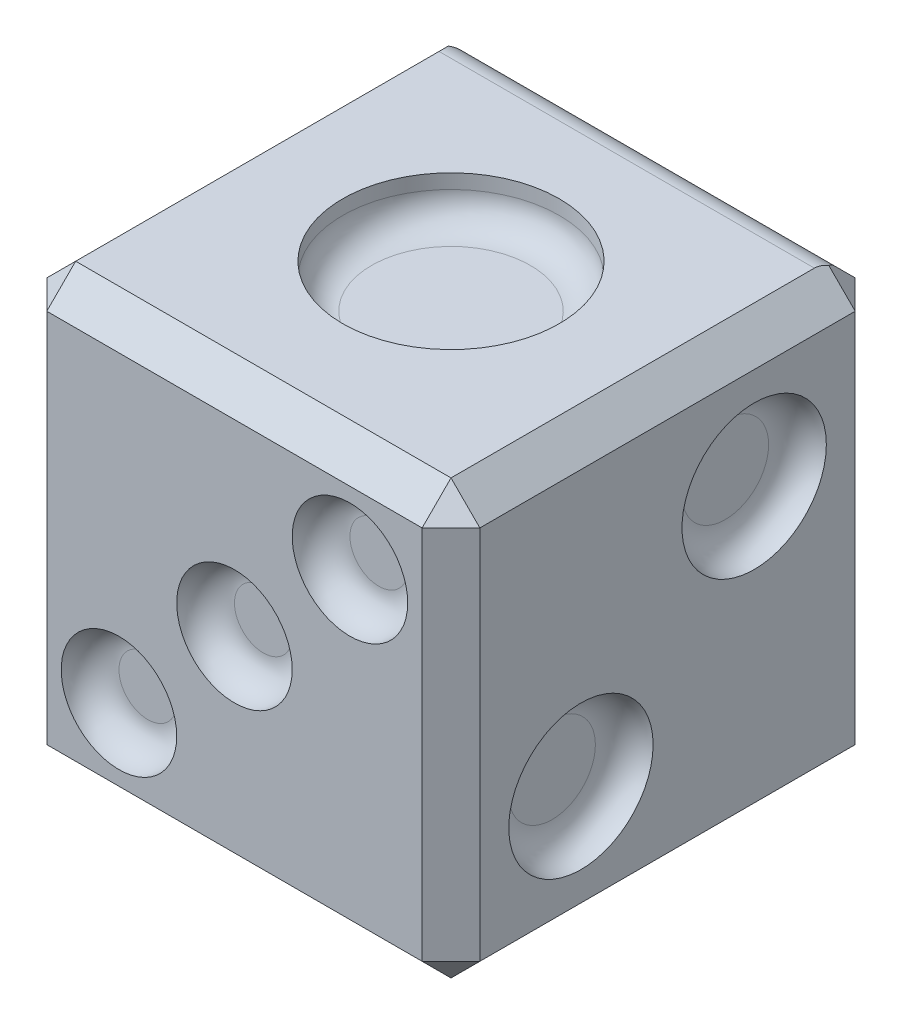
SolidWorks part; units mm, degrees
ref_plane "正面" through (0, 0, 0) normal (0, 0, 1) x (1, 0, 0)
ref_plane "平面" through (0, 0, 0) normal (0, 1, 0) x (1, 0, 0)
ref_plane "右側面" through (0, 0, 0) normal (1, 0, 0) x (0, 0, -1)
sketch "ｽｹｯﾁ7" plane through (0, 0, 0) normal (0, 1, 0) x (1, 0, 0)
  line L1 (0, 0) -> (30, 0)
  line L2 (0, 0) -> (0, 30)
  line L3 (0, 30) -> (30, 30)
  line L4 (30, 0) -> (30, 30)
  dimension "D1" = 30
  dimension "D2" = 30
extrude "ﾎﾞｽ - 押し出し1" add sketch "ｽｹｯﾁ7" along normal blind 30 contours L2 L1 L4 L3
chamfer "面取り2" distance 2 angle 45 12 edges at (0, 15, -30) (0, 15, 0) (30, 15, 0) (0, 30, -15) (15, 30, 0) (30, 30, -15) (15, 30, -30) (30, 15, -30) (0, 0, -15) (15, 0, 0) (30, 0, -15) (15, 0, -30)
sketch "ｽｹｯﾁ11" plane through (0, 30, 0) normal (0, 1, 0) x (1, 0, 0)
  line L0 (2, 28) -> (2, 2) construction
  line L1 (2, 2) -> (28, 2) construction
  circle A0 centre (15, 15) radius 7.5
  dimension "D1" = 15
  dimension "D2" = 13
  dimension "D3" = 13
extrude "ｶｯﾄ - 押し出し4" cut sketch "ｽｹｯﾁ11" against normal blind 3 contours A0
fillet "ﾌｨﾚｯﾄ1" radius 2 1 edges at (15, 27, -7.5)
sketch "ｽｹｯﾁ12" plane through (0, 0, 0) normal (0, 0, 1) x (1, 0, 0)
  line L0 (0, 2) -> (0, 28) construction
  line L1 (28, 0) -> (2, 0) construction
  line L2 (2, 30) -> (28, 30) construction
  line L3 (30, 28) -> (30, 2) construction
  circle A0 centre (23, 23) radius 4
  circle A1 centre (15, 15) radius 4
  circle A2 centre (7, 7) radius 4
  dimension "D3" = 8
  dimension "D6" = 8
  dimension "D9" = 8
  dimension "D1" = 7
  dimension "D2" = 7
  dimension "D4" = 7
  dimension "D5" = 7
  dimension "D7" = 15
  dimension "D8" = 15
extrude "ｶｯﾄ - 押し出し5" cut sketch "ｽｹｯﾁ12" against normal blind 2 contours A0 | A1 | A2
fillet "ﾌｨﾚｯﾄ2" radius 2 3 edges at (27, 23, -2) (19, 15, -2) (11, 7, -2)
sketch3d "3Dｽｹｯﾁ1"
  point P0 (25.9316, 13.2015, 0)
sketch "ｽｹｯﾁ13" plane through (0, 0, 0) normal (0, -1, 0) x (1, 0, 0)
  line L0 (28, -30) -> (2, -30) construction
  line L1 (0, -28) -> (0, -2) construction
  line L2 (30, -2) -> (30, -28) construction
  line L3 (2, 0) -> (28, 0) construction
  circle A0 centre (7.5, -6.5) radius 4
  circle A1 centre (7.5, -15) radius 4
  circle A2 centre (7.5, -23.5) radius 4
  circle A3 centre (22.5, -23.5) radius 4
  circle A4 centre (22.5, -15) radius 4
  circle A5 centre (22.5, -6.5) radius 4
  dimension "D1" = 8
  dimension "D2" = 8
  dimension "D3" = 8
  dimension "D4" = 8
  dimension "D5" = 8
  dimension "D6" = 8
  dimension "D9" = 6.5
  dimension "D16" = 15
  dimension "D7" = 6.5
  dimension "D8" = 7.5
  dimension "D10" = 7.5
  dimension "D11" = 6.5
  dimension "D12" = 7.5
  dimension "D13" = 7.5
  dimension "D14" = 6.5
  dimension "D15" = 7.5
  dimension "D17" = 15
  dimension "D18" = 7.5
extrude "ｶｯﾄ - 押し出し6" cut sketch "ｽｹｯﾁ13" against normal blind 2 contours A0 | A5 | A4 | A3 | A2 | A1
fillet "ﾌｨﾚｯﾄ3" radius 2 7 edges at (22.5, 2, -27.5) (7.5, 2, -27.5) (7.5, 2, -19) (22.5, 2, -19) (22.5, 2, -10.5) (7.5, 2, -10.5) (15, 30, -28)
sketch "ｽｹｯﾁ14" plane through (0, 0, -30) normal (0, 0, -1) x (-1, 0, 0)
  line L0 (-30, 2) -> (-30, 28) construction
  line L1 (-2, 29.4142) -> (-28, 29.4142) construction
  line L2 (0, 28) -> (0, 2) construction
  line L3 (-2, 0) -> (-28, 0) construction
  circle A0 centre (-21.5, 20.9142) radius 4.5
  circle A1 centre (-8.5, 20.9142) radius 4.5
  circle A2 centre (-21.5, 8.5) radius 4.5
  circle A3 centre (-8.5, 8.5) radius 4.5
  dimension "D1" = 9
  dimension "D2" = 9
  dimension "D3" = 9
  dimension "D4" = 9
  dimension "D5" = 8.5
  dimension "D6" = 8.5
  dimension "D7" = 8.5
  dimension "D8" = 8.5
  dimension "D9" = 8.5
  dimension "D10" = 8.5
  dimension "D11" = 8.5
  dimension "D12" = 8.5
extrude "ｶｯﾄ - 押し出し7" cut sketch "ｽｹｯﾁ14" against normal blind 2 contours A0 | A2 | A1 | A3
fillet "ﾌｨﾚｯﾄ4" radius 2 4 edges at (4, 20.9142, -28) (4, 8.5, -28) (17, 8.5, -28) (17, 20.9142, -28)
sketch "ｽｹｯﾁ15" plane through (30, 0, 0) normal (1, 0, 0) x (0, 0, -1)
  line L0 (2, 30) -> (27.1716, 30) construction
  line L1 (30, 28) -> (30, 2) construction
  line L2 (28, 0) -> (2, 0) construction
  line L3 (0, 2) -> (0, 28) construction
  circle A0 centre (21, 21) radius 5
  circle A1 centre (9, 9) radius 5
  dimension "D1" = 10
  dimension "D2" = 10
  dimension "D3" = 9
  dimension "D4" = 9
  dimension "D5" = 9
  dimension "D6" = 9
extrude "ｶｯﾄ - 押し出し8" cut sketch "ｽｹｯﾁ15" against normal blind 2 contours A0 | A1
fillet "ﾌｨﾚｯﾄ5" radius 2 2 edges at (28, 9, -14) (28, 21, -26)
sketch "ｽｹｯﾁ16" plane through (0, 0, 0) normal (-1, 0, 0) x (0, 0, 1)
  line L0 (-2, 0) -> (-28, 0) construction
  line L1 (-30, 2) -> (-30, 28) construction
  line L2 (0, 28) -> (0, 2) construction
  line L3 (-27.1716, 30) -> (-2, 30) construction
  circle A0 centre (-23, 23) radius 4
  circle A1 centre (-23, 7) radius 4
  circle A2 centre (-15, 15) radius 4
  circle A3 centre (-7, 23) radius 4
  circle A4 centre (-7, 7) radius 4
  dimension "D1" = 8
  dimension "D2" = 8
  dimension "D3" = 8
  dimension "D4" = 8
  dimension "D5" = 8
  dimension "D6" = 7
  dimension "D10" = 7
  dimension "D7" = 7
  dimension "D8" = 7
  dimension "D9" = 7
  dimension "D11" = 7
  dimension "D12" = 7
  dimension "D13" = 7
  dimension "D14" = 15
  dimension "D15" = 15
extrude "ｶｯﾄ - 押し出し9" cut sketch "ｽｹｯﾁ16" against normal blind 2 contours A0 | A3 | A2 | A1 | A4
fillet "ﾌｨﾚｯﾄ6" radius 2 5 edges at (2, 7, -19) (2, 7, -3) (2, 15, -11) (2, 23, -3) (2, 23, -19)
